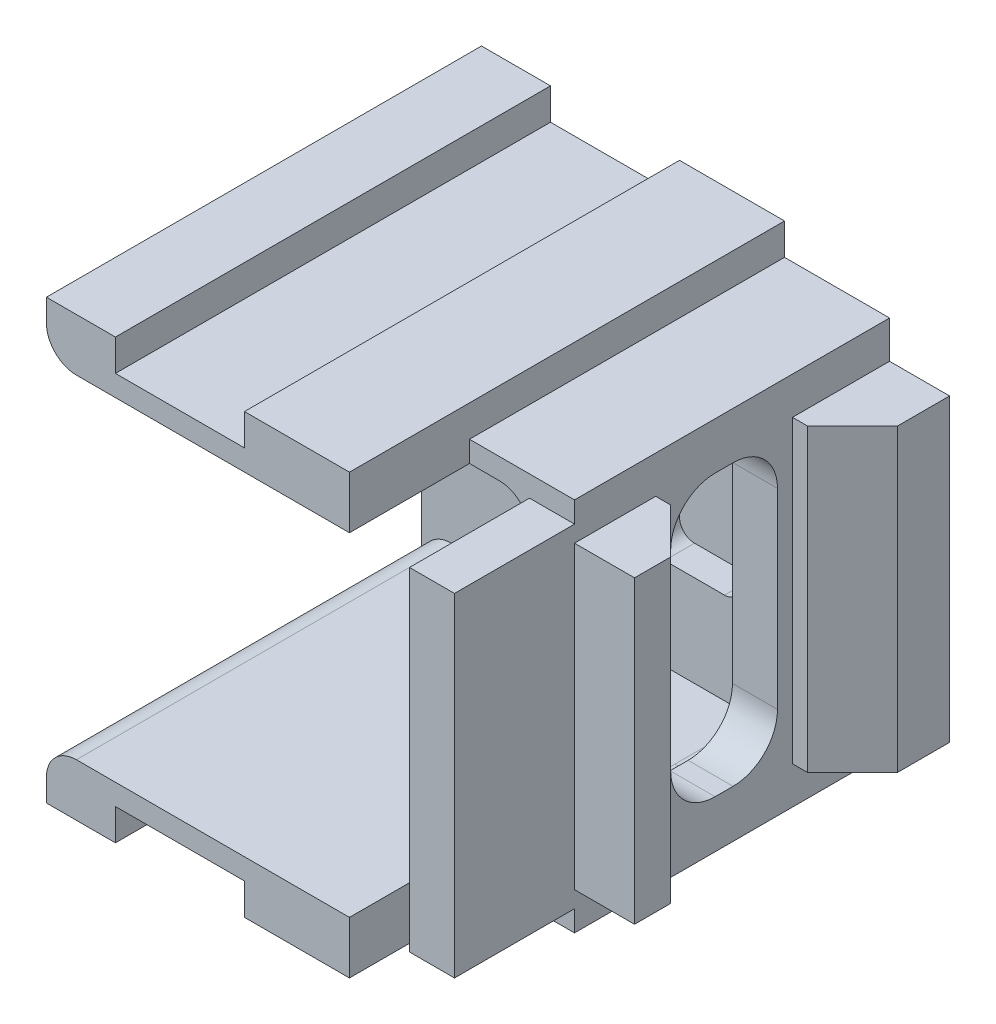
SolidWorks part; units mm, degrees
ref_plane "Front Plane" through (0, 0, 0) normal (1, 0, 0) x (0, 1, 0)
ref_plane "Top Plane" through (0, 0, 0) normal (0, 0, 1) x (0, 1, 0)
ref_plane "Right Plane" through (0, 0, 0) normal (0, 1, 0) x (-1, 0, 0)
sketch "Sketch2" plane through (0, 0, 0) normal (1, 0, 0) x (0, 1, 0)
  line L1 (5, 5.25) -> (-5, 5.25)
  line L2 (5, 5.25) -> (5, -5.25)
  line L3 (5, -5.25) -> (-5, -5.25)
  line L4 (-5, 5.25) -> (-5, -5.25)
  line L5 (5, 5.25) -> (-5, -5.25) construction
  line L6 (5, -5.25) -> (-5, 5.25) construction
  point P0 (0, 0)
  dimension "D1" = 10.5
  dimension "D2" = 10
extrude "Boss-Extrude1" add sketch "Sketch2" along normal blind 2
sketch "Sketch3" plane through (0, 0, 0) normal (-1, 0, 0) x (0, -1, 0)
  line L1 (-6.25, -5.25) -> (6.25, -5.25)
  line L2 (-6.25, -5.25) -> (-6.25, 9.25)
  line L3 (-6.25, 9.25) -> (6.25, 9.25)
  line L4 (5, -5.25) -> (5, 5.25)
  line L5 (5, 5.25) -> (-5, 5.25)
  line L6 (-5, 5.25) -> (-5, -5.25)
  line L7 (-5, -5.25) -> (5, -5.25)
  line L8 (5, -5.25) -> (5, 5.25) construction
  line L9 (5, 5.25) -> (-5, 5.25) construction
  line L10 (-5, 5.25) -> (-5, -5.25) construction
  line L11 (-5, -5.25) -> (5, -5.25) construction
  line L12 (6.25, -5.25) -> (6.25, 9.25)
  point P8 (0, -5.25)
  point P9 (0, -5.25)
  dimension "D2" = 12.5
  dimension "D3" = 14.5
  dimension "D1" = 0
extrude "Boss-Extrude2" add sketch "Sketch3" along normal blind 3.5
sketch "Sketch4" plane through (-3.5, 0, 0) normal (-1, 0, 0) x (0, -1, 0)
  line L1 (-7.3, -5.25) -> (7.3, -5.25)
  line L2 (-7.3, -5.25) -> (-7.3, 9.25)
  line L3 (-7.3, 9.25) -> (7.3, 9.25)
  line L4 (-6.25, 9.25) -> (-6.25, -5.25)
  line L5 (-6.25, -5.25) -> (6.25, -5.25)
  line L6 (6.25, -5.25) -> (6.25, 9.25)
  line L7 (6.25, 9.25) -> (-6.25, 9.25)
  line L8 (-6.25, 9.25) -> (-6.25, -5.25) construction
  line L9 (-6.25, -5.25) -> (6.25, -5.25) construction
  line L10 (6.25, -5.25) -> (6.25, 9.25) construction
  line L11 (6.25, 9.25) -> (-6.25, 9.25) construction
  line L12 (7.3, -5.25) -> (7.3, 9.25)
  point P9 (0, -5.25)
  point P10 (0, -5.25)
  dimension "D2" = 14.6
  dimension "D1" = 0
extrude "Boss-Extrude3" add sketch "Sketch4" along normal blind 3.5
sketch "Sketch5" plane through (-7, 0, 0) normal (-1, 0, 0) x (0, -1, 0)
  line L1 (-6.25, -5.25) -> (6.25, -5.25)
  line L2 (-6.25, -5.25) -> (-6.25, 9.25)
  line L3 (-6.25, 9.25) -> (6.25, 9.25)
  line L4 (-7.3, 9.25) -> (-7.3, -5.25)
  line L5 (-7.3, -5.25) -> (7.3, -5.25)
  line L6 (7.3, -5.25) -> (7.3, 9.25)
  line L7 (7.3, 9.25) -> (-7.3, 9.25)
  line L8 (-7.3, 9.25) -> (-7.3, -5.25) construction
  line L9 (-7.3, -5.25) -> (7.3, -5.25) construction
  line L10 (7.3, -5.25) -> (7.3, 9.25) construction
  line L11 (7.3, 9.25) -> (-7.3, 9.25) construction
  line L12 (6.25, -5.25) -> (6.25, 9.25)
  point P8 (0, -5.25)
  point P9 (0, -5.25)
  dimension "D2" = 12.5
  dimension "D1" = 0
extrude "Boss-Extrude4" add sketch "Sketch5" along normal blind 4.3
sketch "Sketch6" plane through (-11.3, 0, 0) normal (-1, 0, 0) x (0, -1, 0)
  line L0 (6.25, 9.25) -> (6.25, -5.25) construction
  line L1 (6.25, -5.25) -> (7.3, -5.25) construction
  line L2 (7.3, -5.25) -> (7.3, 9.25) construction
  line L3 (7.3, 9.25) -> (6.25, 9.25) construction
  line L4 (-6.25, 9.25) -> (-6.25, -5.25) construction
  line L5 (-6.25, -5.25) -> (6.25, -5.25) construction
  line L6 (6.25, -5.25) -> (6.25, 9.25) construction
  line L7 (6.25, 9.25) -> (-6.25, 9.25) construction
  line L8 (-6.25, -5.25) -> (-6.25, 9.25) construction
  line L9 (-6.25, 9.25) -> (-7.3, 9.25) construction
  line L10 (-7.3, 9.25) -> (-7.3, -5.25) construction
  line L11 (-7.3, -5.25) -> (-6.25, -5.25) construction
  line L12 (6.25, 9.25) -> (6.25, -5.25) construction
  line L13 (6.25, -5.25) -> (7.3, -5.25)
  line L14 (7.3, -5.25) -> (7.3, 9.25)
  line L15 (7.3, 9.25) -> (6.25, 9.25)
  line L16 (-6.25, 9.25) -> (-6.25, -5.25) construction
  line L17 (-6.25, -5.25) -> (6.25, -5.25)
  line L18 (6.25, -5.25) -> (6.25, 9.25) construction
  line L19 (6.25, 9.25) -> (-6.25, 9.25)
  line L20 (-6.25, -5.25) -> (-6.25, 9.25) construction
  line L21 (-6.25, 9.25) -> (-7.3, 9.25)
  line L22 (-7.3, 9.25) -> (-7.3, -5.25)
  line L23 (-7.3, -5.25) -> (-6.25, -5.25)
extrude "Boss-Extrude5" add sketch "Sketch6" along normal blind 2.3
sketch "Sketch8" plane through (0, 0, 9.25) normal (0, 0, 1) x (1, 0, 0)
  line L1 (-13.6, 5.55) -> (-1.5, 5.55)
  line L2 (-13.6, 5.55) -> (-13.6, -5.55)
  line L3 (-13.6, -5.55) -> (-1.5, -5.55)
  line L4 (-1.5, 5.55) -> (-1.5, -5.55)
  line L16 (0, -6.25) -> (0, 6.25)
  line L17 (0, 6.25) -> (-3.5, 6.25)
  line L18 (-3.5, 6.25) -> (-3.5, 7.3)
  line L19 (-3.5, 7.3) -> (-7, 7.3)
  line L20 (-7, 7.3) -> (-7, 6.25)
  line L21 (-7, 6.25) -> (-11.3, 6.25)
  line L22 (-11.3, 6.25) -> (-11.3, 7.3)
  line L23 (-11.3, 7.3) -> (-13.6, 7.3)
  line L24 (-13.6, 7.3) -> (-13.6, -7.3)
  line L25 (-13.6, -7.3) -> (-11.3, -7.3)
  line L26 (-11.3, -7.3) -> (-11.3, -6.25)
  line L27 (-11.3, -6.25) -> (-7, -6.25)
  line L28 (-7, -6.25) -> (-7, -7.3)
  line L29 (-7, -7.3) -> (-3.5, -7.3)
  line L30 (-3.5, -7.3) -> (-3.5, -6.25)
  line L31 (-3.5, -6.25) -> (0, -6.25)
  line L32 (0, -6.25) -> (0, 6.25) construction
  line L33 (0, 6.25) -> (-3.5, 6.25) construction
  line L34 (-3.5, 6.25) -> (-3.5, 7.3) construction
  line L35 (-3.5, 7.3) -> (-7, 7.3) construction
  line L36 (-7, 7.3) -> (-7, 6.25) construction
  line L37 (-7, 6.25) -> (-11.3, 6.25) construction
  line L38 (-11.3, 6.25) -> (-11.3, 7.3) construction
  line L39 (-11.3, 7.3) -> (-13.6, 7.3) construction
  line L40 (-13.6, 7.3) -> (-13.6, -7.3) construction
  line L41 (-13.6, -7.3) -> (-11.3, -7.3) construction
  line L42 (-11.3, -7.3) -> (-11.3, -6.25) construction
  line L43 (-11.3, -6.25) -> (-7, -6.25) construction
  line L44 (-7, -6.25) -> (-7, -7.3) construction
  line L45 (-7, -7.3) -> (-3.5, -7.3) construction
  line L46 (-3.5, -7.3) -> (-3.5, -6.25) construction
  line L47 (-3.5, -6.25) -> (0, -6.25) construction
  point P10 (-13.6, 0)
  point P12 (-13.6, 0)
  dimension "D2" = 0.7
  dimension "D3" = 1.5
  dimension "D1" = 0
extrude "Cut-Extrude1" cut sketch "Sketch8" against normal blind 13
sketch "Sketch10" plane through (0, 0, 9.25) normal (0, 0, 1) x (1, 0, 0)
  line L0 (-1.5, 5.55) -> (-13.6, 5.55) construction
  line L9 (0, 6.25) -> (-3.5, 6.25)
  line L10 (0, 6.25) -> (0, 5.55)
  line L11 (0, 5.55) -> (-3.5, 5.55)
  line L12 (-3.5, 6.25) -> (-3.5, 5.55)
  line L13 (-13.6, -5.55) -> (-1.5, -5.55) construction
  line L14 (0, -6.25) -> (-3.5, -6.25)
  line L15 (0, -6.25) -> (0, -5.55)
  line L16 (0, -5.55) -> (-3.5, -5.55)
  line L17 (-3.5, -6.25) -> (-3.5, -5.55)
extrude "Cut-Extrude6" cut sketch "Sketch10" against normal up to surface (4 mm away) up to face at (1, 0, 5.25)
fillet "Fillet1" radius 1 2 edges at (-13.6, -5.55, 2.75) (-13.6, 5.55, 2.75)
sketch "Sketch13" plane through (0, 0, 0) normal (1, 0, 0) x (0, 0, -1)
  line L0 (-1.845, 0.01) -> (-1.845, -3.18) construction
  line L1 (-0.565, -4.46) -> (0.035, -4.46) construction
  line L2 (1.315, -3.18) -> (1.315, 0.01) construction
  line L3 (1.315, 3.2) -> (1.315, 0.01) construction
  line L4 (-0.565, 4.48) -> (0.035, 4.48) construction
  line L5 (-1.845, 0.01) -> (-1.845, 3.2) construction
  line L6 (-1.845, 0.01) -> (-1.845, -3.18) construction
  line L7 (-0.565, -4.46) -> (0.035, -4.46) construction
  line L8 (1.315, -3.18) -> (1.315, 0.01) construction
  line L9 (1.315, 3.2) -> (1.315, 0.01) construction
  line L10 (-0.565, 4.48) -> (0.035, 4.48) construction
  line L11 (-1.845, 0.01) -> (-1.845, 3.2) construction
  line L12 (-2.045, 0.01) -> (-2.045, -3.18)
  line L13 (-0.565, -4.66) -> (0.035, -4.66)
  line L14 (1.515, -3.18) -> (1.515, 0.01)
  line L15 (1.515, 3.2) -> (1.515, 0.01)
  line L16 (-0.565, 4.68) -> (0.035, 4.68)
  line L17 (-2.045, 0.01) -> (-2.045, 3.2)
  arc A0 (-1.845, -3.18) -> (-0.565, -4.46) centre (-0.565, -3.18) ccw construction
  arc A1 (0.035, -4.46) -> (1.315, -3.18) centre (0.035, -3.18) ccw construction
  arc A2 (1.315, 3.2) -> (0.035, 4.48) centre (0.035, 3.2) ccw construction
  arc A3 (-0.565, 4.48) -> (-1.845, 3.2) centre (-0.565, 3.2) ccw construction
  arc A4 (-1.845, -3.18) -> (-0.565, -4.46) centre (-0.565, -3.18) ccw construction
  arc A5 (0.035, -4.46) -> (1.315, -3.18) centre (0.035, -3.18) ccw construction
  arc A6 (1.315, 3.2) -> (0.035, 4.48) centre (0.035, 3.2) ccw construction
  arc A7 (-0.565, 4.48) -> (-1.845, 3.2) centre (-0.565, 3.2) ccw construction
  arc A8 (-2.045, -3.18) -> (-0.565, -4.66) centre (-0.565, -3.18) ccw
  arc A9 (0.035, -4.66) -> (1.515, -3.18) centre (0.035, -3.18) ccw
  arc A10 (1.515, 3.2) -> (0.035, 4.68) centre (0.035, 3.2) ccw
  arc A11 (-0.565, 4.68) -> (-2.045, 3.2) centre (-0.565, 3.2) ccw
  dimension "D1" = 0.2
extrude "Cut-Extrude9" cut sketch "Sketch13" against normal through all both and the other way through all
sketch "Sketch15" plane through (0, 0, -3.75) normal (0, 0, 1) x (1, 0, 0)
  line L1 (-3, 2.5) -> (-6, 2.5)
  line L2 (-3, 2.5) -> (-3, -2.5)
  line L3 (-3, -2.5) -> (-6, -2.5)
  line L4 (-13.6, 6.55) -> (-13.6, -6.55)
  line L5 (-12.6, -5.55) -> (-1.5, -5.55)
  line L6 (-1.5, -5.55) -> (-1.5, 5.55)
  line L7 (-1.5, 5.55) -> (-12.6, 5.55)
  line L8 (-13.6, 6.55) -> (-13.6, -6.55)
  line L9 (-12.6, -5.55) -> (-1.5, -5.55)
  line L10 (-1.5, -5.55) -> (-1.5, 5.55)
  line L11 (-1.5, 5.55) -> (-12.6, 5.55)
  line L12 (-6, 2.5) -> (-6, -2.5)
  arc A2 (-12.6, -5.55) -> (-13.6, -6.55) centre (-12.6, -6.55) ccw
  arc A3 (-13.6, 6.55) -> (-12.6, 5.55) centre (-12.6, 6.55) ccw
  arc A4 (-12.6, -5.55) -> (-13.6, -6.55) centre (-12.6, -6.55) ccw
  arc A5 (-13.6, 6.55) -> (-12.6, 5.55) centre (-12.6, 6.55) ccw
  point P12 (-1.5, 0)
  point P13 (-3, 0)
  dimension "D2" = 1.5
  dimension "D3" = 3
  dimension "D4" = 5
  dimension "D1" = 0
extrude "Boss-Extrude6" add sketch "Sketch15" along normal blind 0.5
fillet "Fillet5" radius 0.5 4 edges at (-6, 2.5, -3.5) (-6, -2.5, -3.5) (-3, 2.5, -3.5) (-3, -2.5, -3.5)
fillet "Fillet3" radius 1 2 edges at (-1.5, 5.55, 1) (-1.5, -5.55, 1)
sketch "Sketch14" plane through (2, 0, 0) normal (1, 0, 0) x (0, 0, -1)
  line L0 (-5.25, -5) -> (5.25, -5) construction
  line L1 (-2.545, -5) -> (2.015, -5)
  line L2 (-2.545, -5) -> (-2.545, 5)
  line L3 (-2.545, 5) -> (2.015, 5)
  line L4 (2.015, -5) -> (2.015, 5)
  line L5 (5.25, 5) -> (-5.25, 5) construction
  line L6 (-2.045, 3.2) -> (-2.045, -3.18) construction
  line L7 (1.515, -3.18) -> (1.515, 3.2) construction
  dimension "D1" = 0.5
  dimension "D2" = 0.5
extrude "Cut-Extrude10" cut sketch "Sketch14" against normal up to surface (2 mm away) and the other way through all up to face at (0, 0, 2.4167)
chamfer "Chamfer4" distance 1.5 angle 45 2 edges at (2, 0, -2.015) (2, 0, 2.545)
sketch "Sketch16" plane through (0, 0, -3.75) normal (0, 0, 1) x (1, 0, 0)
  line L4 (-3.5, 2.5) -> (-5.5, 2.5)
  line L5 (-6, 2) -> (-6, -2)
  line L6 (-5.5, -2.5) -> (-3.5, -2.5)
  line L7 (-3, -2) -> (-3, 2)
  line L8 (-3.5, 2.5) -> (-5.5, 2.5)
  line L9 (-6, 2) -> (-6, -2)
  line L10 (-5.5, -2.5) -> (-3.5, -2.5)
  line L11 (-3, -2) -> (-3, 2)
  arc A4 (-5.5, 2.5) -> (-6, 2) centre (-5.5, 2) ccw
  arc A5 (-6, -2) -> (-5.5, -2.5) centre (-5.5, -2) ccw
  arc A6 (-3.5, -2.5) -> (-3, -2) centre (-3.5, -2) ccw
  arc A7 (-3, 2) -> (-3.5, 2.5) centre (-3.5, 2) ccw
  arc A8 (-5.5, 2.5) -> (-6, 2) centre (-5.5, 2) ccw
  arc A9 (-6, -2) -> (-5.5, -2.5) centre (-5.5, -2) ccw
  arc A10 (-3.5, -2.5) -> (-3, -2) centre (-3.5, -2) ccw
  arc A11 (-3, 2) -> (-3.5, 2.5) centre (-3.5, 2) ccw
  dimension "D1" = 0
extrude "Cut-Extrude11" cut sketch "Sketch16" against normal blind 0.5
